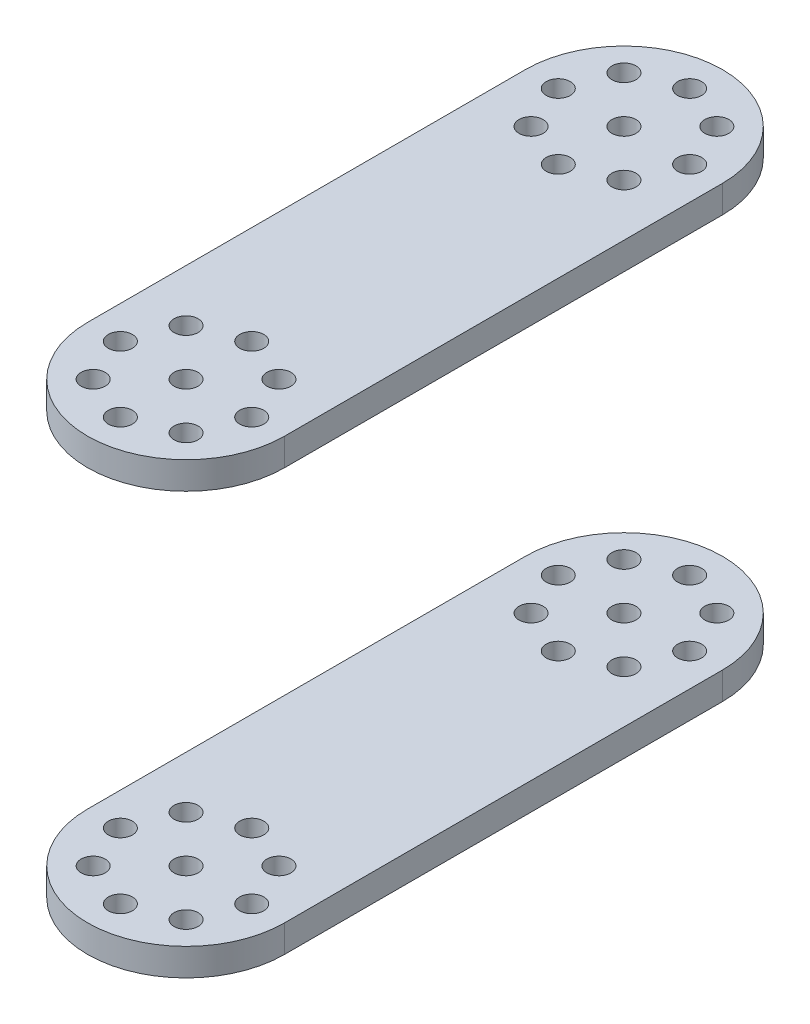
SolidWorks part; units mm, degrees
material "ABS"
ref_plane "正面" through (0, 0, 0) normal (0, 0, 1) x (1, 0, 0)
ref_plane "平面" through (0, 0, 0) normal (0, 1, 0) x (1, 0, 0)
ref_plane "右側面" through (0, 0, 0) normal (1, 0, 0) x (0, 0, -1)
sketch "ｽｹｯﾁ1" plane through (0, 0, 0) normal (0, 1, 0) x (1, 0, 0)
  line L0 (-9, 40) -> (-9, 0)
  line L2 (-10.5, 10.5) -> (-10.5, -10.5) construction
  line L8 (9, 0) -> (9, 40)
  arc A4 (9, 40) -> (-9, 40) centre (0, 40) ccw
  circle A5 centre (0, 40) radius 6 construction
  circle A6 centre (0, 46) radius 1.1
  circle A7 centre (4.2426, 44.2426) radius 1.1
  circle A8 centre (6, 40) radius 1.1
  circle A9 centre (4.2426, 35.7574) radius 1.1
  circle A10 centre (0, 34) radius 1.1
  circle A11 centre (-4.2426, 35.7574) radius 1.1
  circle A12 centre (-6, 40) radius 1.1
  circle A13 centre (-4.2426, 44.2426) radius 1.1
  circle A14 centre (0, 40) radius 1.1
  circle A15 centre (0, 0) radius 1.1
  arc A16 (-9, 0) -> (9, 0) centre (0, 0) ccw
  circle A17 centre (0, 0) radius 6 construction
  circle A18 centre (0, 6) radius 1.1
  circle A19 centre (4.2426, 4.2426) radius 1.1
  circle A20 centre (6, 0) radius 1.1
  circle A21 centre (4.2426, -4.2426) radius 1.1
  circle A22 centre (0, -6) radius 1.1
  circle A23 centre (-4.2426, -4.2426) radius 1.1
  circle A24 centre (-6, 0) radius 1.1
  circle A25 centre (-4.2426, 4.2426) radius 1.1
  point P8 (4.6158, -5.1436)
  point P9 (0, 0)
  point P35 (0, 40)
  point P48 (0, 0)
  dimension "D2" = 9
  dimension "D3" = 2.2
  dimension "D4" = 40
  dimension "D5" = 12
  dimension "D10" = 12
  dimension "D11" = 2.2
  dimension "D13" = 2.2
  dimension "D6" = 2.2
  dimension "D7" = 8
  dimension "D12" = 8
extrude "ﾎﾞｽ - 押し出し1" add sketch "ｽｹｯﾁ1" along normal blind 2.5
ref_plane "平面1" through (0, -36, 0) normal (0, 1, 0) x (1, 0, 0)
sketch "ｽｹｯﾁ2" plane through (0, -36, 0) normal (0, 1, 0) x (1, 0, 0)
  line L3 (9, 0) -> (9, 40)
  line L5 (-9, 40) -> (-9, 0)
  line L6 (9, 0) -> (9, 40)
  line L8 (-9, 40) -> (-9, 0)
  circle A0 centre (0, 40) radius 1.1
  arc A1 (9, 40) -> (-9, 40) centre (0, 40) ccw
  arc A2 (9, 40) -> (-9, 40) centre (0, 40) ccw
  circle A3 centre (0, 40) radius 6 construction
  circle A4 centre (0, 46) radius 1.1
  circle A5 centre (4.2426, 44.2426) radius 1.1
  circle A6 centre (6, 40) radius 1.1
  circle A11 centre (0, 0) radius 1.1 construction
  circle A12 centre (0, 0) radius 1.1
  arc A13 (-9, 0) -> (9, 0) centre (0, 0) ccw
  arc A14 (-9, 0) -> (9, 0) centre (0, 0) ccw
  circle A15 centre (0, 0) radius 6 construction
  circle A16 centre (0, 6) radius 1.1
  circle A17 centre (4.2426, 4.2426) radius 1.1
  circle A18 centre (6, 0) radius 1.1
  circle A19 centre (4.2426, -4.2426) radius 1.1
  circle A20 centre (0, -6) radius 1.1
  circle A21 centre (-4.2426, -4.2426) radius 1.1
  circle A22 centre (-6, 0) radius 1.1
  circle A23 centre (-4.2426, 4.2426) radius 1.1
  circle A24 centre (4.2426, 35.7574) radius 1.1
  circle A25 centre (0, 34) radius 1.1
  circle A26 centre (-4.2426, 35.7574) radius 1.1
  circle A27 centre (-6, 40) radius 1.1
  circle A28 centre (-4.2426, 44.2426) radius 1.1
  point P30 (0, 0)
  point P31 (15.057, 38.2477)
  point P32 (0, 0)
  point P33 (0, 46)
  point P48 (0, 40)
  dimension "D2" = 2.2
  dimension "D3" = 12
  dimension "D4" = 2.2
  dimension "D5" = 12
  dimension "D6" = 8
  dimension "D7" = 2.2
  dimension "D1" = 0
extrude "ﾎﾞｽ - 押し出し2" add sketch "ｽｹｯﾁ2" against normal blind 2.5 separate body
